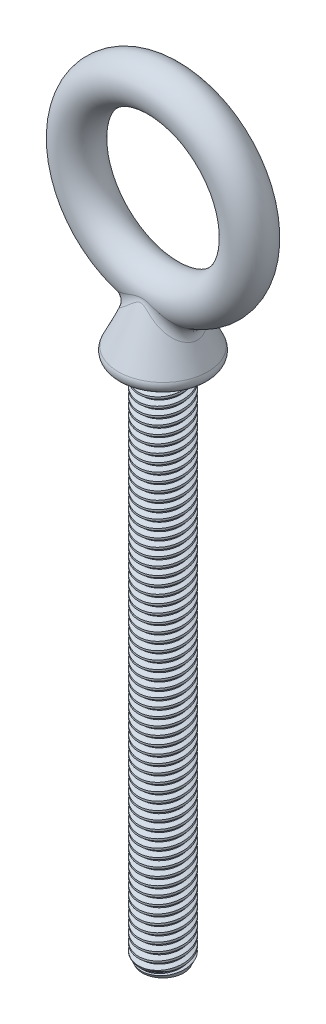
SolidWorks part; units mm, degrees
ref_plane "Front" through (0, 0, 0) normal (0, 0, 1) x (1, 0, 0)
ref_plane "Top" through (0, 0, 0) normal (0, 1, 0) x (1, 0, 0)
ref_plane "Right" through (0, 0, 0) normal (1, 0, 0) x (0, 0, -1)
sketch "Sketch1" plane through (0, 0, 0) normal (-1, 0, 0) x (0, 1, 0)
  line L0 (-21.0344, 0) -> (-12.7, 0) construction
  line L1 (-12.7, 0) -> (0, 0) construction
  line L2 (0, 10.2426) -> (0, -9.3978) construction
  circle A0 centre (-16.8672, 0) radius 4.1672
  circle A1 centre (16.8672, 0) radius 4.1672 construction
  dimension "D1" = 8.3344
  dimension "D3" = 8.3344
  dimension "Eye OD" = 42.0688
  dimension "Eye ID" = 25.4
revolve "Revolve1" add sketch "Sketch1" angle 360 about L2
sketch "Sketch3" plane through (0, 0, 0) normal (1, 0, 0) x (0, 0, -1)
  line L0 (-4.1672, -16.8672) -> (-8.7398, -26.6868)
  line L1 (-7.2832, -28.9719) -> (-4.7625, -28.9719)
  line L2 (0, -130.5719) -> (0, -16.8672)
  line L3 (0, -16.8672) -> (-4.1672, -16.8672)
  line L4 (0, 0) -> (0, -80.8733) construction
  line L5 (-4.7625, -28.9719) -> (-4.7625, -130.5719)
  line L6 (-4.7625, -130.5719) -> (0, -130.5719)
  line L7 (-7.2832, -28.9719) -> (-9.8039, -28.9719) construction
  line L8 (-9.8039, -28.9719) -> (-8.7398, -26.6868) construction
  line L9 (4.7625, -28.9719) -> (4.7625, -130.5719) construction
  arc A0 (-8.7398, -26.6868) -> (-7.2832, -28.9719) centre (-7.2832, -27.3651) ccw
  circle A1 centre (0, -16.8672) radius 4.1672 construction
  circle A2 centre (0, 16.8672) radius 4.1672 construction
  dimension "Shoulder Dia" = 17.78
  dimension "Thread Dia" = 9.525
  dimension "Overall Length" = 151.6062
  dimension "Shank Length" = 101.6
revolve "Revolve2" add sketch "Sketch3" angle 360 about L4
fillet "Fillet1" radius 2.0836 1 edges at (4.5198, -19.39, 2.8475)
sketch "Sketch4" plane through (0, 0, 0) normal (1, 0, 0) x (0, 0, -1)
  line L0 (-4.7625, -28.9719) -> (4.7625, -28.9719) construction
  line L1 (4.7625, -28.9719) -> (4.7951, -29.1676) construction
  line L2 (4.7951, -29.1676) -> (5.0235, -30.5378)
  line L3 (5.0235, -30.5378) -> (4.0944, -30.1897)
  line L4 (4.0944, -30.1897) -> (4.0291, -29.7982)
  line L5 (4.0291, -29.7982) -> (4.7951, -29.1676)
  line L6 (4.9093, -29.8527) -> (4.0617, -29.994) construction
  line L7 (-4.7625, -28.9719) -> (-4.7625, -30.5594) construction
  line L8 (-4.7625, -30.5594) -> (4.7625, -28.9719) construction
  line L9 (-4.7625, -28.9719) -> (-4.7625, -130.5719) construction
  line L10 (4.7625, -28.9719) -> (4.7625, -130.5719) construction
  line L12 (-4.7625, -31.4647) -> (4.7625, -29.8772) construction
  line L13 (-0.2832, -28.9719) -> (0.2832, -32.3699) construction
  line L15 (-4.7625, -130.5719) -> (0, -130.5719) construction
  point P19 (0, -30.6709)
  dimension "D1" = 60
  dimension "D2" = 0.1984
  dimension "Thread Pitch" = 1.5875
  dimension "D3" = 0.3969
  dimension "D4" = 1.5875
  dimension "Thread Length" = 101.6
revolve "Cut-Revolve1" cut sketch "Sketch4" angle 360 about L13
sketch "Sketch5" plane through (0, 0, 0) normal (1, 0, 0) x (0, 0, -1)
  line L0 (4.0291, -130.5719) -> (4.7625, -130.5719)
  line L1 (4.7625, -130.5719) -> (4.7625, -128.9991)
  line L2 (4.7625, -128.9991) -> (4.0291, -130.5719)
  line L3 (4.7625, -28.9719) -> (4.7625, -130.5719) construction
  line L4 (-4.7625, -130.5719) -> (0, -130.5719) construction
  line L5 (0, 0) -> (0, -130.5719) construction
  dimension "D1" = 25
revolve "Cut-Revolve2" cut sketch "Sketch5" angle 360 about L5
pattern_linear "LPattern1" count 64 spacing 1.5875 along (0, -1, 0) of "Cut-Revolve1"
sketch "Sketch6" plane through (0, 0, 0) normal (0, 0, 1) x (1, 0, 0)
  line L0 (-21.0344, 0) -> (-12.7, 0)
  line L1 (12.7, 0) -> (21.0344, 0)
  arc A0 (21.0344, 0) -> (-21.0344, 0) centre (0, 0) ccw
  arc A1 (12.7, 0) -> (-12.7, 0) centre (0, 0) ccw
equation "\"D1@Fillet1\"=\"D3@Sketch1\"/4"
equation "\"D2@Sketch4\"=\"Thread Pitch@Sketch4\"/8"
equation "\"D3@Sketch4\"=\"Thread Pitch@Sketch4\"/4"
equation "\"D4@Sketch4\"=\"Thread Pitch@Sketch4\""
equation "\"D3@LPattern1\"=\"Thread Pitch@Sketch4\""
equation "\"D1@LPattern1\"=\"Thread Length@Sketch4\"/\"Thread Pitch@Sketch4\""
